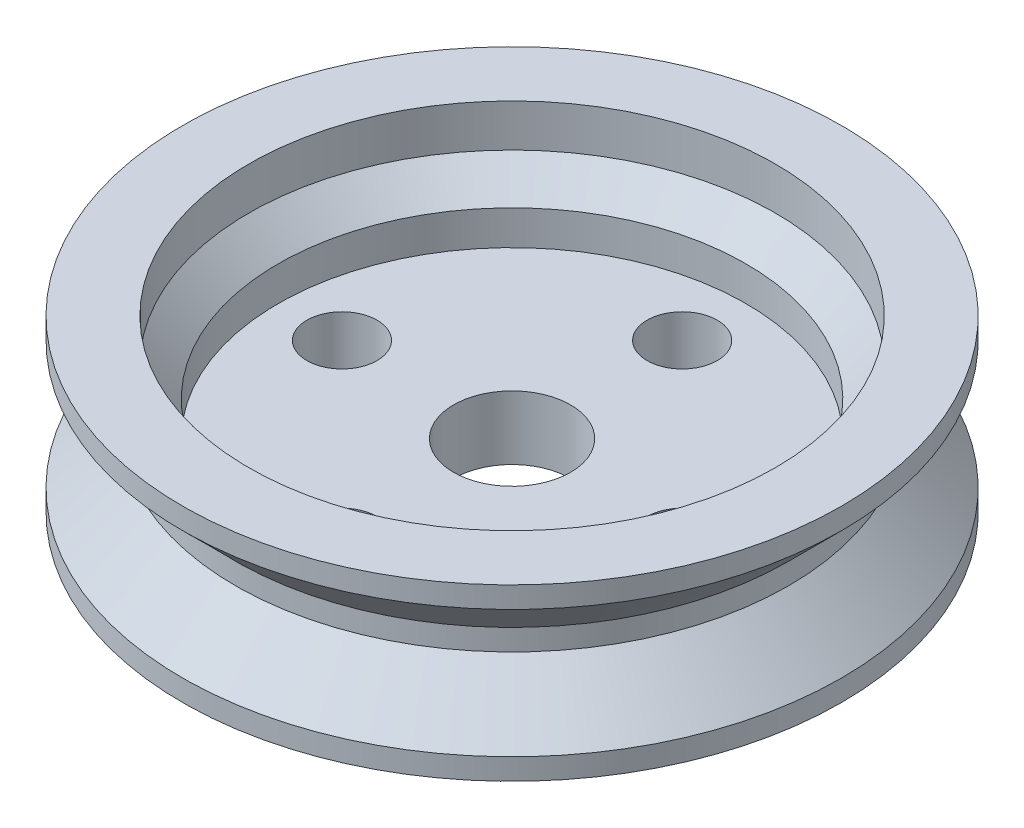
SolidWorks part; units mm, degrees
ref_plane "前视基准面" through (0, 0, 0) normal (0, 0, 1) x (1, 0, 0)
ref_plane "上视基准面" through (0, 0, 0) normal (0, 1, 0) x (1, 0, 0)
ref_plane "右视基准面" through (0, 0, 0) normal (1, 0, 0) x (0, 0, -1)
sketch "草图2" plane through (0, 0, 0) normal (0, 0, 1) x (1, 0, 0)
  line L0 (0, 0) -> (-15.5, 0)
  line L1 (-15.5, 0) -> (-15.5, 1)
  line L2 (-15.5, 1) -> (-13, 3.5)
  line L3 (-13, 3.5) -> (-13, 4.5)
  line L4 (-13, 4.5) -> (-15.5, 7)
  line L5 (-15.5, 7) -> (-15.5, 8)
  line L6 (-15.5, 8) -> (-12.3787, 8)
  line L11 (-11, 4.6213) -> (-12.3787, 6)
  line L12 (-12.3787, 6) -> (-12.3787, 8)
  line L15 (0, 0) -> (0, 1.5)
  line L16 (-13, 4) -> (-18.965, 4) construction
  line L18 (-11, 3) -> (-11, 4.6213)
  line L19 (-11, 3) -> (0, 3)
  line L20 (0, 3) -> (0, 1.5)
  dimension "D2" = 1.5
  dimension "D3" = 2
  dimension "D4" = 11
  dimension "D5" = 1
  dimension "D6" = 1
  dimension "D7" = 15.5
  dimension "D8" = 3
  dimension "D9" = 1
  dimension "D10" = 45
  dimension "D11" = 2
revolve "旋转1" add sketch "草图2" angle 360 about L15
ref_axis "基准轴1" through (0, 8, 0) along (0, -1, 0)
sketch "草图3" plane through (0, 0, 0) normal (0, -1, 0) x (1, 0, 0)
  circle A0 centre (0, 0) radius 2.75
  circle A1 centre (0, 8) radius 1.65
  circle A2 centre (8, 0) radius 1.65
  circle A3 centre (0, -8) radius 1.65
  circle A4 centre (-8, 0) radius 1.65
  point P14 (0, 0)
  dimension "D1" = 5.5
  dimension "D2" = 3.3
  dimension "D3" = 8
  dimension "D4" = 4
extrude "切除-拉伸1" cut sketch "草图3" against normal through all contours A1 | A4 | A3 | A2 | A0
